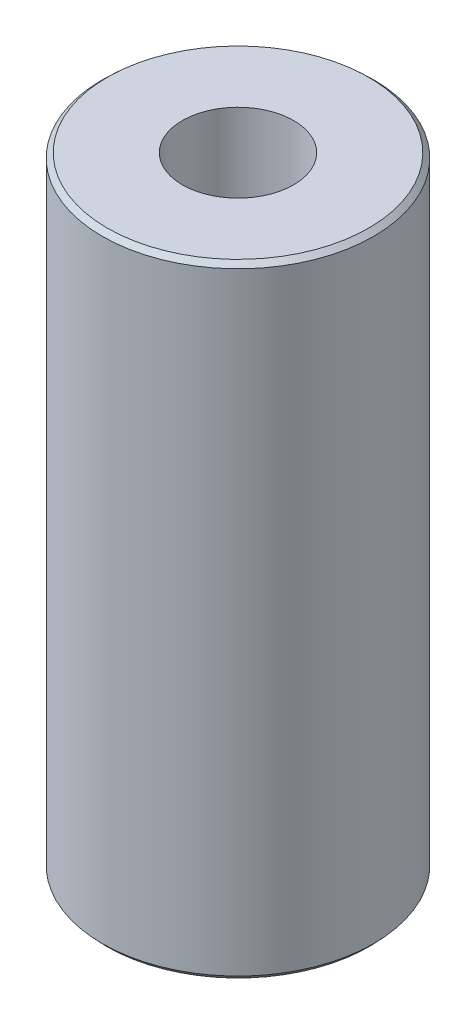
SolidWorks part; units mm, degrees
ref_plane "Front Plane" through (0, 0, 0) normal (0, 0, 1) x (1, 0, 0)
ref_plane "Top Plane" through (0, 0, 0) normal (0, 1, 0) x (1, 0, 0)
ref_plane "Right Plane" through (0, 0, 0) normal (1, 0, 0) x (0, 0, -1)
sketch "Sketch1" plane through (0, 0, 0) normal (0, 1, 0) x (1, 0, 0)
  circle A0 centre (0, 0) radius 50
  dimension "SHAFT_OD" = 100
extrude "Boss-Extrude1" add sketch "Sketch1" along normal blind 229.325
sketch "Sketch2" plane through (0, 0, 0) normal (0, 1, 0) x (1, 0, 0)
  circle A0 centre (0, 0) radius 20.5275
  dimension "BORE_D" = 41.055
extrude "Cut-Extrude1" cut sketch "Sketch2" along normal through all
chamfer "Chamfer1" distance 1.7116 angle 46.984 2 edges at (0, 229.325, 50) (0, 0, 50) first distance on face at (0, 229.325, 50) first distance on face at (0, 0, 20.5275)
